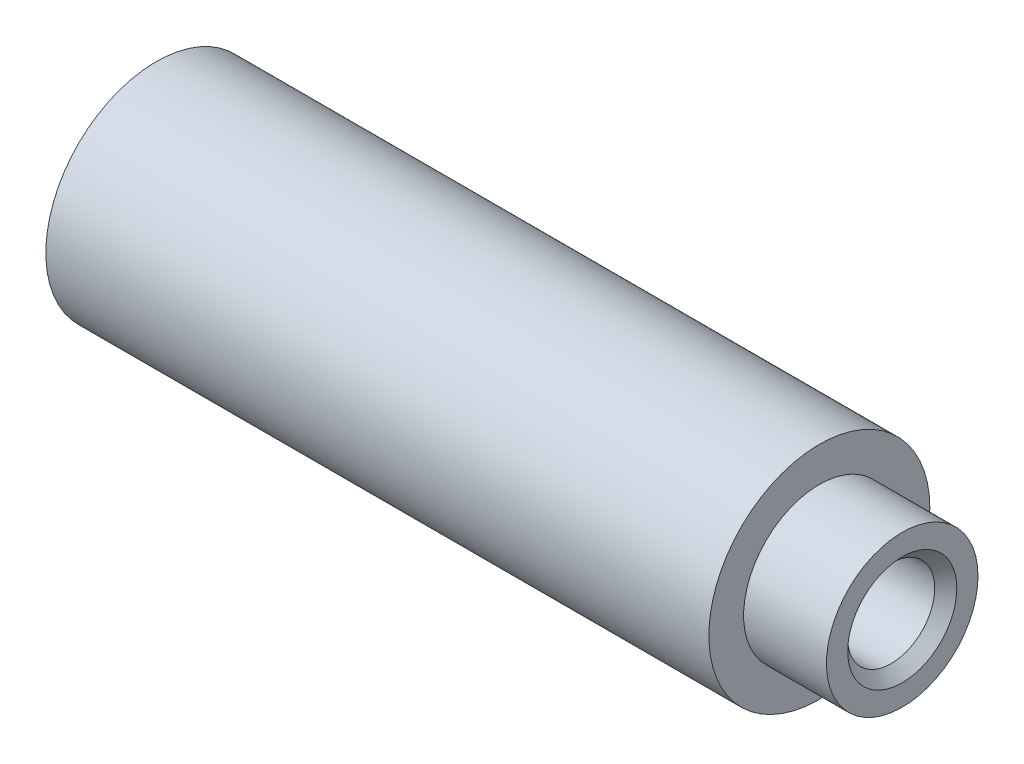
SolidWorks part; units mm, degrees
ref_plane "Ebene vorne" through (0, 0, 0) normal (0, 0, 1) x (1, 0, 0)
ref_plane "Ebene oben" through (0, 0, 0) normal (0, 1, 0) x (1, 0, 0)
ref_plane "Ebene rechts" through (0, 0, 0) normal (1, 0, 0) x (0, 0, -1)
sketch "Skizze1" plane through (0, 0, 0) normal (1, 0, 0) x (0, 0, -1)
  circle A0 centre (0, 0) radius 1.575
  circle A1 centre (0, 0) radius 4
  dimension "D1" = 8
  dimension "D2" = 3.15
extrude "Aufsatz-Linear austragen1" add sketch "Skizze1" along normal blind 27
sketch "Skizze2" plane through (27, 0, 0) normal (1, 0, 0) x (0, 0, -1)
  circle A0 centre (0, 0) radius 2.7425
  dimension "D1" = 5.485
extrude "Schnitt-Linear austragen1" cut sketch "Skizze2" against normal blind 3 flip side to cut
chamfer "Fase1" distance 0.4 angle 45 2 edges at (0, 0, -1.575) (27, 0, -1.575)
